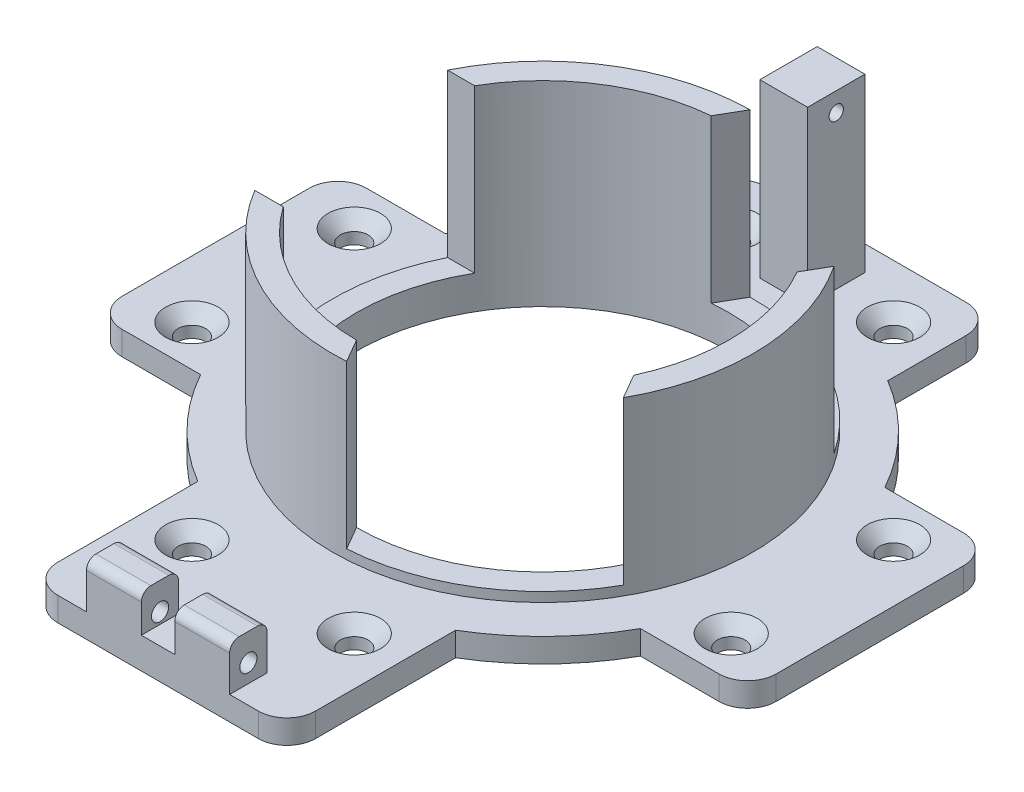
SolidWorks part; units mm, degrees
ref_plane "Front Plane" through (0, 0, 0) normal (0, 0, 1) x (1, 0, 0)
ref_plane "Top Plane" through (0, 0, 0) normal (0, 1, 0) x (1, 0, 0)
ref_plane "Right Plane" through (0, 0, 0) normal (1, 0, 0) x (0, 0, -1)
sketch "Sketch1" plane through (0, 0, 0) normal (0, 1, 0) x (1, 0, 0)
  line L0 (18.9157, -18.3445) -> (-18.9157, 18.3445) construction
  line L1 (-34.2532, 12.8) -> (-23.0322, 12.8)
  line L2 (-34.2532, 12.8) -> (-34.2532, -12.8)
  line L3 (-34.2532, -12.8) -> (-23.0322, -12.8)
  line L4 (34.2532, 12.8) -> (34.2532, -12.8)
  line L5 (-18.9157, -18.3445) -> (18.9157, 18.3445) construction
  line L7 (-13.5, 33.85) -> (13.5, 33.85)
  line L8 (-13.5, 33.85) -> (-13.5, 22.629)
  line L9 (-13.5, -40.29) -> (13.5, -40.29)
  line L10 (13.5, 33.85) -> (13.5, 22.629)
  line L14 (13.5, -22.629) -> (13.5, -40.29)
  line L15 (23.0322, -12.8) -> (34.2532, -12.8)
  line L16 (23.0322, 12.8) -> (34.2532, 12.8)
  line L19 (-13.5, -22.629) -> (-13.5, -40.29)
  circle A0 centre (0, 0) radius 19.5
  circle A1 centre (0, 0) radius 22
  arc A2 (-13.5, 22.629) -> (-23.0322, 12.8) centre (0, 0) ccw
  arc A3 (-23.0322, -12.8) -> (-13.5, -22.629) centre (0, 0) ccw
  arc A4 (23.0322, 12.8) -> (13.5, 22.629) centre (0, 0) ccw
  arc A5 (13.5, -22.629) -> (23.0322, -12.8) centre (0, 0) ccw
  dimension "D1" = 39
  dimension "D2" = 44
  dimension "D3" = 52.7
  dimension "D4" = 25.6
  dimension "D6" = 74.14
  dimension "D7" = 27
  dimension "D9" = 27.49
extrude "Boss-Extrude3" add sketch "Sketch1" along normal blind 2.5 contours L3 A3 L19 L9 L14 A5 L15 L4 L16 A4 L10 L7 L8 A2 L1 L2
extrude "Boss-Extrude4" add sketch "Sketch1<6>" along normal blind 20.5 contours A0 | A1
sketch "Sketch1<6>" plane through (0, 0, 0) normal (0, 1, 0) x (1, 0, 0) same geometry as "Sketch1"
sketch "Sketch33" plane through (0, 0, 0) normal (1, 0, 0) x (0, 0, -1)
  line L0 (-11.2463, 20.5) -> (9.7537, 20.5)
  line L1 (-11.2463, 20.5) -> (-11.2463, 3.5)
  line L2 (9.7537, 20.5) -> (9.7537, 3.5)
  line L3 (-11.2463, 3.5) -> (9.7537, 3.5)
  line L4 (19.5, 20.5) -> (-19.5, 20.5) construction
  line L5 (22, 20.5) -> (-22, 20.5) construction
  dimension "D1" = 17
  dimension "D2" = 21
extrude "Cut-Extrude2" cut sketch "Sketch33" against normal up to next contours L0 L1 L3 L2
pattern_circular "CirPattern1" count 3 every 120 about axis through (0, 20.5, 0) along (0, 1, 0) of "Cut-Extrude2"
extrude "Cut-Extrude1" cut sketch "Sketch1<7>" along normal blind 18 contours A0
sketch "Sketch1<7>" plane through (0, 0, 0) normal (0, 1, 0) x (1, 0, 0) same geometry as "Sketch1"
sketch "Sketch12" plane through (0, 2.5, 0) normal (0, 1, 0) x (1, 0, 0)
  line L0 (0, 0) -> (8.5, 28.2395) construction
  line L1 (-13.5, 33.85) -> (-13.5, 22.629) construction
  line L2 (13.5, 33.85) -> (13.5, 22.629) construction
  line L3 (0, 0) -> (28.2395, -8.5) construction
  line L4 (0, 0) -> (8.5, 28.2395) construction
  point P0 (-8.5, 28.2395)
  point P1 (8.5, 28.2395)
  point P8 (-13.5, 28.2395)
  point P10 (28.2395, 8.5)
  point P11 (28.2395, -8.5)
  point P12 (8.5, -28.2395)
  point P13 (-8.5, -28.2395)
  point P14 (-28.2395, -8.5)
  point P15 (-28.2395, 8.5)
  point P16 (0, 0)
  dimension "D1" = 5
  dimension "D2" = 5
  dimension "D4" = 90
  dimension "D5" = 29.491
  dimension "D3" = 4
hole_wizard "CSK for M2.5 Countersunk Flat Head Screw1" positions "Sketch13" profile "Sketch14" countersink size "M2.5" standard "ISO" end condition through all
sketch "Sketch13" plane through (0, 2.5, 0) normal (0, 1, 0) x (1, 0, 0)
  point P0 (-8.5, 28.2395)
  point P3 (8.5, 28.2395)
  point P6 (28.2395, 8.5)
  point P9 (28.2395, -8.5)
  point P12 (8.5, -28.2395)
  point P15 (-8.5, -28.2395)
  point P18 (-28.2395, 8.5)
  point P21 (-28.2395, -8.5)
sketch "Sketch14" plane through (-8.5, 2.5, -28.2395) normal (1, 0, 0) x (0, 0, 1)
  line L0 (0, 0) -> (0, 2.5)
  line L1 (0, 2.5) -> (1.45, 2.5)
  line L2 (1.45, 2.5) -> (1.45, 1.3)
  line L3 (1.45, 1.3) -> (2.75, 0)
  line L5 (2.75, 0) -> (0, 0)
  line L6 (-1.45, 1.3) -> (-2.75, 0) construction
  line L11 (0, -6.35) -> (0, 107.95) construction
  dimension "Thru Hole Dia." = 2.9
  dimension "Thru Hole Depth" = 2.5
  dimension "Near C'Sink Dia." = 5.5
  dimension "Near C'Sink Angle" = 90
sketch "Sketch15" plane through (0, 2.5, 0) normal (0, 1, 0) x (1, 0, 0)
  line L0 (-13.5, -40.29) -> (13.5, -40.29) construction
  line L1 (-7.5, -40.29) -> (-1.75, -40.29)
  line L2 (-7.5, -40.29) -> (-7.5, -36.4029)
  line L3 (-7.5, -36.4029) -> (-1.75, -36.4029)
  line L4 (-1.75, -40.29) -> (-1.75, -36.4029)
  line L5 (-13.5, -22.629) -> (-13.5, -40.29) construction
  line L6 (1.75, -40.29) -> (7.5, -40.29)
  line L7 (1.75, -40.29) -> (1.75, -36.3715)
  line L8 (1.75, -36.3715) -> (7.5, -36.3715)
  line L9 (7.5, -40.29) -> (7.5, -36.3715)
  line L10 (-1.75, -40.29) -> (1.75, -40.29)
  line L11 (-1.75, -40.29) -> (-1.75, -33.1745)
  line L12 (-1.75, -33.1745) -> (1.75, -33.1745)
  line L13 (1.75, -40.29) -> (1.75, -33.1745)
  line L14 (13.5, -22.629) -> (13.5, -40.29) construction
  line M26 (-13.5, -40.29) -> (13.5, -40.29)
  dimension "D1" = 6
  dimension "D2" = 5.75
  dimension "D3" = 6
  dimension "D4" = 5.75
  dimension "D5" = 3.5
extrude "Boss-Extrude5" add sketch "Sketch15" along normal blind 4.75 contours L9 L8 L7 M26 | L2 L1 L4 L3 region at (4.625, 2.5, 38.3307)
sketch "Sketch16" plane through (0, 2.5, 0) normal (0, 1, 0) x (1, 0, 0)
  line L1 (-1.75, -40.29) -> (1.75, -40.29)
  line L2 (-1.75, -40.29) -> (-1.75, -33.29)
  line L3 (-1.75, -33.29) -> (1.75, -33.29)
  line L4 (1.75, -40.29) -> (1.75, -33.29)
  dimension "D1" = 3.5
  dimension "D2" = 7
extrude "Boss-Extrude6" add sketch "Sketch16" along normal blind 0.75
fillet "Fillet1" radius 3 1 edges at (34.2532, 1.25, 12.8) type face fillet first side face at (34.2532, 1.25, 0) second side face at (28.6427, 1.25, 12.8)
fillet "Fillet2" radius 3 1 edges at (34.2532, 1.25, -12.8) type face fillet first side face at (34.2532, 1.25, -1.5) second side face at (28.6427, 1.25, -12.8)
fillet "Fillet3" radius 3 1 edges at (13.5, 1.25, -33.85) type face fillet first side face at (13.5, 1.25, -28.2395) second side face at (0, 1.25, -33.85)
fillet "Fillet4" radius 3 1 edges at (-13.5, 1.25, -33.85) type face fillet first side face at (-1.5, 1.25, -33.85) second side face at (-13.5, 1.25, -28.2395)
fillet "Fillet5" radius 3 1 edges at (-34.2532, 1.25, -12.8) type face fillet first side face at (-28.6427, 1.25, -12.8) second side face at (-34.2532, 1.25, 0)
fillet "Fillet6" radius 3 1 edges at (-34.2532, 1.25, 12.8) type face fillet first side face at (-34.2532, 1.25, 1.5) second side face at (-28.6427, 1.25, 12.8)
fillet "Fillet7" radius 3 1 edges at (-13.5, 1.25, 40.29) type face fillet first side face at (-13.5, 1.25, 31.4595) second side face at (0, 3.7917, 40.29)
fillet "Fillet8" radius 3 1 edges at (13.5, 1.25, 40.29) type face fillet first side face at (13.5, 1.25, 31.4595) second side face at (0.5, 3.7917, 40.29)
fillet "Fillet9" radius 1 1 edges at (-4.625, 7.25, 36.4029) type face fillet first side face at (-4.05, 4.55, 36.4029) second side face at (-4.625, 7.25, 38.3465)
fillet "Fillet10" radius 1 1 edges at (-4.625, 7.25, 40.29) type face fillet first side face at (0, 3.7917, 40.29) second side face at (-4.625, 7.25, 38.8465)
fillet "Fillet11" radius 1 1 edges at (4.625, 7.25, 40.29) type face fillet first side face at (0, 3.625, 40.29) second side face at (4.625, 7.25, 38.3307)
fillet "Fillet12" radius 1 1 edges at (4.625, 7.25, 36.3715) type face fillet first side face at (4.625, 7.25, 37.8307) second side face at (4.05, 4.55, 36.3715)
sketch "Sketch17" plane through (7.5, 0, 0) normal (1, 0, 0) x (0, 0, -1)
  line L0 (-40.29, 2.5) -> (-36.3715, 2.5) construction
  point P0 (-38.3307, 4.4)
  point P5 (-38.3307, 2.5)
  dimension "D1" = 1.9
hole_wizard "Ø1.8 (1.8) Diameter Hole2" positions "Sketch20" profile "Sketch21" hole size "Ø1.8" standard "ISO" end condition through all
sketch "Sketch20" plane through (7.5, 0, 0) normal (1, 0, 0) x (0, 0, -1)
  point P0 (-38.3307, 4.4)
sketch "Sketch21" plane through (7.5, 4.4, 38.3307) normal (0, 1, 0) x (0, 0, -1)
  line L0 (0, 0) -> (0, 41.7532)
  line L1 (0, 41.7532) -> (0.9, 41.7532)
  line L2 (0.9, 41.7532) -> (0.9, 0)
  line L5 (0.9, 0) -> (0, 0)
  line L11 (0, -6.35) -> (0, 107.95) construction
  dimension "Thru Hole Dia." = 1.8
  dimension "Thru Hole Depth" = 41.7532
sketch "Sketch22" plane through (0, 2.5, 0) normal (0, 1, 0) x (1, 0, 0)
  line L0 (-13.5, 33.85) -> (13.5, 33.85) construction
  line L1 (2.5, 25.2395) -> (-2.5, 25.2395)
  line L2 (2.5, 25.2395) -> (2.5, 31.2395)
  line L3 (2.5, 31.2395) -> (-2.5, 31.2395)
  line L4 (-2.5, 25.2395) -> (-2.5, 31.2395)
  point P4 (0, 31.2395)
  point P7 (0, 33.85)
  point P8 (2.5, 28.2395)
  dimension "D1" = 5
  dimension "D2" = 6
extrude "Boss-Extrude7" add sketch "Sketch22" along normal blind 18
sketch "Sketch26" plane through (-2.5, 0, 0) normal (-1, 0, 0) x (0, 0, 1)
  line L0 (-31.2395, 20.5) -> (-25.2395, 20.5) construction
  point P0 (-28.2395, 18.5)
  point P3 (-28.2395, 20.5)
  dimension "D1" = 2
hole_wizard "Ø1.5 (1.5) Diameter Hole1" positions "Sketch27" profile "Sketch28" hole size "Ø1.5" standard "ISO" end condition through all
sketch "Sketch27" plane through (-2.5, 0, 0) normal (-1, 0, 0) x (0, 0, 1)
  point P0 (-28.2395, 18.5)
sketch "Sketch28" plane through (-2.5, 18.5, -28.2395) normal (0, 1, 0) x (0, 0, 1)
  line L0 (0, 0) -> (0, 36.7532)
  line L1 (0, 36.7532) -> (0.75, 36.7532)
  line L2 (0.75, 36.7532) -> (0.75, 0)
  line L5 (0.75, 0) -> (0, 0)
  line L11 (0, -6.35) -> (0, 107.95) construction
  dimension "Thru Hole Dia." = 1.5
  dimension "Thru Hole Depth" = 36.7532
